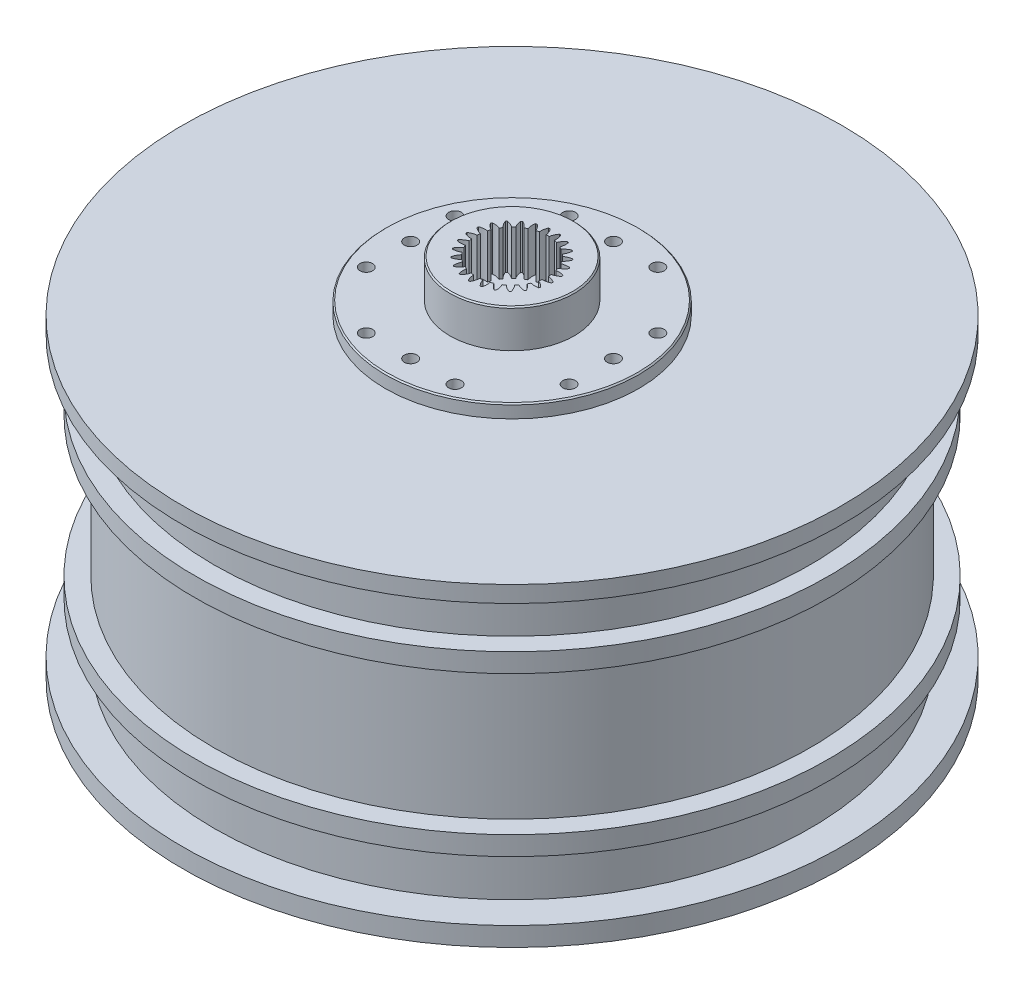
SolidWorks part; units mm, degrees
material "ABS"
ref_plane "正面" through (0, 0, 0) normal (0, 0, 1) x (1, 0, 0)
ref_plane "平面" through (0, 0, 0) normal (0, 1, 0) x (1, 0, 0)
ref_plane "右側面" through (0, 0, 0) normal (1, 0, 0) x (0, 0, -1)
sketch "ｽｹｯﾁ1" plane through (0, 0, 0) normal (0, 1, 0) x (1, 0, 0)
  circle A0 centre (0, 0) radius 10
extrude "ﾎﾞｽ - 押し出し1" add sketch "ｽｹｯﾁ1" along normal blind 2
sketch "ｽｹｯﾁ2" plane through (0, 2, 0) normal (0, 1, 0) x (1, 0, 0)
  circle A0 centre (0, 0) radius 4.9
extrude "ﾎﾞｽ - 押し出し2" add sketch "ｽｹｯﾁ2" along normal blind 3
sketch "ｽｹｯﾁ3" plane through (0, 0, 0) normal (0, -1, 0) x (1, 0, 0)
  line L0 (0, 8) -> (-3.5, 8) construction
  line L1 (0, 0) -> (0, 8) construction
  line L2 (0, 8) -> (3.5, 8) construction
  circle A0 centre (-3.5, 8) radius 0.5
  circle A1 centre (0, 8) radius 0.5
  circle A2 centre (3.5, 8) radius 0.5
  circle A3 centre (8, 0) radius 0.5
  circle A4 centre (8, 3.5) radius 0.5
  circle A5 centre (8, -3.5) radius 0.5
  circle A6 centre (0, -8) radius 0.5
  circle A7 centre (3.5, -8) radius 0.5
  circle A8 centre (-3.5, -8) radius 0.5
  circle A9 centre (-8, 0) radius 0.5
  circle A10 centre (-8, -3.5) radius 0.5
  circle A11 centre (-8, 3.5) radius 0.5
  point P29 (0, 0)
  dimension "D1" = 4
extrude "ｶｯﾄ - 押し出し1" cut sketch "ｽｹｯﾁ3" against normal blind 3
sketch "ｽｹｯﾁ4" plane through (0, 0, 0) normal (0, -1, 0) x (1, 0, 0)
  circle A0 centre (0, 0) radius 4.35
  circle A1 centre (0, 0) radius 2.9
  circle A2 centre (0, 0) radius 1.4
extrude "ｶｯﾄ - 押し出し2" cut sketch "ｽｹｯﾁ4" against normal through all contours A2 region at (0, 0, 0)
extrude "ｶｯﾄ - 押し出し3" cut sketch "ｽｹｯﾁ4<3>" against normal blind 0.45 contours A0 A1 region at (-4.227, 0, 0)
sketch "ｽｹｯﾁ4<3>" plane through (0, 0, 0) normal (0, -1, 0) x (1, 0, 0) same geometry as "ｽｹｯﾁ4"
extrude "ｶｯﾄ - 押し出し4" cut sketch "ｽｹｯﾁ4<4>" against normal blind 0.95 contours A1 A2 region at (-2.818, 0, 0)
sketch "ｽｹｯﾁ4<4>" plane through (0, 0, 0) normal (0, -1, 0) x (1, 0, 0) same geometry as "ｽｹｯﾁ4"
sketch "ｽｹｯﾁ6" plane through (0, 5, 0) normal (0, 1, 0) x (1, 0, 0)
  line L3 (-0.2102, 3.1179) -> (-0.391, 3.0951) construction
  arc A0 (0.1175, 2.809) -> (-0.1175, 2.809) centre (0, 0) ccw
  arc A1 (0.3689, 3.3803) -> (-0.3689, 3.3803) centre (0, 0) ccw
  circle A2 centre (0, 0) radius 3.125 construction
  circle A3 centre (0, 0) radius 2.9365 construction
  arc A4 (-0.1175, 2.809) -> (-0.3689, 3.3803) centre (-1.3511, 2.6072) ccw
  arc A5 (0.3689, 3.3803) -> (0.1175, 2.809) centre (1.3511, 2.6072) ccw
  arc A6 (1.1979, 3.1824) -> (0.8124, 2.6916) centre (1.9571, 2.1893) ccw
  arc A7 (0.8124, 2.6916) -> (0.5847, 2.75) centre (0, 0) ccw
  arc A8 (0.5847, 2.75) -> (0.4834, 3.3659) centre (-0.6603, 2.8613) ccw
  arc A9 (1.1979, 3.1824) -> (0.4834, 3.3659) centre (0, 0) ccw
  arc A10 (1.9517, 2.7845) -> (1.4563, 2.405) centre (2.4401, 1.6338) ccw
  arc A11 (1.4563, 2.405) -> (1.2503, 2.5182) centre (0, 0) ccw
  arc A12 (1.2503, 2.5182) -> (1.3052, 3.1399) centre (0.072, 2.9357) ccw
  arc A13 (1.9517, 2.7845) -> (1.3052, 3.1399) centre (0, 0) ccw
  arc A14 (2.5829, 2.2116) -> (2.0086, 1.9672) centre (2.7697, 0.9757) ccw
  arc A15 (2.0086, 1.9672) -> (1.8372, 2.1282) centre (0, 0) ccw
  arc A16 (1.8372, 2.1282) -> (2.0451, 2.7167) centre (0.7998, 2.8255) ccw
  arc A17 (2.5829, 2.2116) -> (2.0451, 2.7167) centre (0, 0) ccw
  arc A18 (3.0518, 1.4998) -> (2.4347, 1.4059) centre (2.9253, 0.2562) ccw
  arc A19 (2.4347, 1.4059) -> (2.3088, 1.6044) centre (0, 0) ccw
  arc A20 (2.3088, 1.6044) -> (2.6565, 2.1227) centre (1.4774, 2.5378) ccw
  arc A21 (3.0518, 1.4998) -> (2.6565, 2.1227) centre (0, 0) ccw
  arc A22 (3.3289, 0.6938) -> (2.7079, 0.7563) centre (2.8972, -0.4793) ccw
  arc A23 (2.7079, 0.7563) -> (2.6352, 0.9798) centre (0, 0) ccw
  arc A24 (2.6352, 0.9798) -> (3.1009, 1.3954) centre (2.0621, 2.0907) ccw
  arc A25 (3.3289, 0.6938) -> (3.1009, 1.3954) centre (0, 0) ccw
  arc A26 (3.3968, -0.1559) -> (2.8109, 0.0591) centre (2.6869, -1.1848) ccw
  arc A27 (2.8109, 0.0591) -> (2.7961, 0.2937) centre (0, 0) ccw
  arc A28 (2.7961, 0.2937) -> (3.3505, 0.5804) centre (2.5173, 1.5122) ccw
  arc A29 (3.3968, -0.1559) -> (3.3505, 0.5804) centre (0, 0) ccw
  arc A30 (3.2513, -0.9958) -> (2.7373, -0.6418) centre (2.3079, -1.8158) ccw
  arc A31 (2.7373, -0.6418) -> (2.7813, -0.4109) centre (0, 0) ccw
  arc A32 (2.7813, -0.4109) -> (3.3896, -0.2711) centre (2.8142, 0.8387) ccw
  arc A33 (3.2513, -0.9958) -> (3.3896, -0.2711) centre (0, 0) ccw
  arc A34 (2.9016, -1.7731) -> (2.4917, -1.3024) centre (1.7838, -2.3327) ccw
  arc A35 (2.4917, -1.3024) -> (2.5917, -1.0897) centre (0, 0) ccw
  arc A36 (2.5917, -1.0897) -> (3.2157, -1.1055) centre (2.9344, 0.1124) ccw
  arc A37 (2.9016, -1.7731) -> (3.2157, -1.1055) centre (0, 0) ccw
  arc A38 (2.3695, -2.4389) -> (2.0895, -1.8811) centre (1.1477, -2.703) ccw
  arc A39 (2.0895, -1.8811) -> (2.2393, -1.7) centre (0, 0) ccw
  arc A40 (2.2393, -1.7) -> (2.8397, -1.8705) centre (2.8702, -0.6208) ccw
  arc A41 (2.3695, -2.4389) -> (2.8397, -1.8705) centre (0, 0) ccw
  arc A42 (1.6885, -2.9516) -> (1.556, -2.3416) centre (0.4394, -2.9035) ccw
  arc A43 (1.556, -2.3416) -> (1.7462, -2.2035) centre (0, 0) ccw
  arc A44 (1.7462, -2.2035) -> (2.2853, -2.5179) centre (2.6256, -1.3151) ccw
  arc A45 (1.6885, -2.9516) -> (2.2853, -2.5179) centre (0, 0) ccw
  arc A46 (0.9014, -3.2787) -> (0.9248, -2.655) centre (-0.2965, -2.9215) ccw
  arc A47 (0.9248, -2.655) -> (1.1434, -2.5685) centre (0, 0) ccw
  arc A48 (1.1434, -2.5685) -> (1.5874, -3.0072) centre (2.216, -1.9268) ccw
  arc A49 (0.9014, -3.2787) -> (1.5874, -3.0072) centre (0, 0) ccw
  arc A50 (0.0577, -3.3999) -> (0.2355, -2.8016) centre (-1.0137, -2.756) ccw
  arc A51 (0.2355, -2.8016) -> (0.4687, -2.7722) centre (0, 0) ccw
  arc A52 (0.4687, -2.7722) -> (0.7896, -3.3074) centre (1.6673, -2.4173) ccw
  arc A53 (0.0577, -3.3999) -> (0.7896, -3.3074) centre (0, 0) ccw
  arc A54 (-0.7896, -3.3074) -> (-0.4687, -2.7722) centre (-1.6673, -2.4173) ccw
  arc A55 (-0.4687, -2.7722) -> (-0.2355, -2.8016) centre (0, 0) ccw
  arc A56 (-0.2355, -2.8016) -> (-0.0577, -3.3999) centre (1.0137, -2.756) ccw
  arc A57 (-0.7896, -3.3074) -> (-0.0577, -3.3999) centre (0, 0) ccw
  arc A58 (-1.5874, -3.0072) -> (-1.1434, -2.5685) centre (-2.216, -1.9268) ccw
  arc A59 (-1.1434, -2.5685) -> (-0.9248, -2.655) centre (0, 0) ccw
  arc A60 (-0.9248, -2.655) -> (-0.9014, -3.2787) centre (0.2965, -2.9215) ccw
  arc A61 (-1.5874, -3.0072) -> (-0.9014, -3.2787) centre (0, 0) ccw
  arc A62 (-2.2853, -2.5179) -> (-1.7462, -2.2035) centre (-2.6256, -1.3151) ccw
  arc A63 (-1.7462, -2.2035) -> (-1.556, -2.3416) centre (0, 0) ccw
  arc A64 (-1.556, -2.3416) -> (-1.6885, -2.9516) centre (-0.4394, -2.9035) ccw
  arc A65 (-2.2853, -2.5179) -> (-1.6885, -2.9516) centre (0, 0) ccw
  arc A66 (-2.8397, -1.8705) -> (-2.2393, -1.7) centre (-2.8702, -0.6208) ccw
  arc A67 (-2.2393, -1.7) -> (-2.0895, -1.8811) centre (0, 0) ccw
  arc A68 (-2.0895, -1.8811) -> (-2.3695, -2.4389) centre (-1.1477, -2.703) ccw
  arc A69 (-2.8397, -1.8705) -> (-2.3695, -2.4389) centre (0, 0) ccw
  arc A70 (-3.2157, -1.1055) -> (-2.5917, -1.0897) centre (-2.9344, 0.1124) ccw
  arc A71 (-2.5917, -1.0897) -> (-2.4917, -1.3024) centre (0, 0) ccw
  arc A72 (-2.4917, -1.3024) -> (-2.9016, -1.7731) centre (-1.7838, -2.3327) ccw
  arc A73 (-3.2157, -1.1055) -> (-2.9016, -1.7731) centre (0, 0) ccw
  arc A74 (-3.3896, -0.2711) -> (-2.7813, -0.4109) centre (-2.8142, 0.8387) ccw
  arc A75 (-2.7813, -0.4109) -> (-2.7373, -0.6418) centre (0, 0) ccw
  arc A76 (-2.7373, -0.6418) -> (-3.2513, -0.9958) centre (-2.3079, -1.8158) ccw
  arc A77 (-3.3896, -0.2711) -> (-3.2513, -0.9958) centre (0, 0) ccw
  arc A78 (-3.3505, 0.5804) -> (-2.7961, 0.2937) centre (-2.5173, 1.5122) ccw
  arc A79 (-2.7961, 0.2937) -> (-2.8109, 0.0591) centre (0, 0) ccw
  arc A80 (-2.8109, 0.0591) -> (-3.3968, -0.1559) centre (-2.6869, -1.1848) ccw
  arc A81 (-3.3505, 0.5804) -> (-3.3968, -0.1559) centre (0, 0) ccw
  arc A82 (-3.1009, 1.3954) -> (-2.6352, 0.9798) centre (-2.0621, 2.0907) ccw
  arc A83 (-2.6352, 0.9798) -> (-2.7079, 0.7563) centre (0, 0) ccw
  arc A84 (-2.7079, 0.7563) -> (-3.3289, 0.6938) centre (-2.8972, -0.4793) ccw
  arc A85 (-3.1009, 1.3954) -> (-3.3289, 0.6938) centre (0, 0) ccw
  arc A86 (-2.6565, 2.1227) -> (-2.3088, 1.6044) centre (-1.4774, 2.5378) ccw
  arc A87 (-2.3088, 1.6044) -> (-2.4347, 1.4059) centre (0, 0) ccw
  arc A88 (-2.4347, 1.4059) -> (-3.0518, 1.4998) centre (-2.9253, 0.2562) ccw
  arc A89 (-2.6565, 2.1227) -> (-3.0518, 1.4998) centre (0, 0) ccw
  arc A90 (-2.0451, 2.7167) -> (-1.8372, 2.1282) centre (-0.7998, 2.8255) ccw
  arc A91 (-1.8372, 2.1282) -> (-2.0086, 1.9672) centre (0, 0) ccw
  arc A92 (-2.0086, 1.9672) -> (-2.5829, 2.2116) centre (-2.7697, 0.9757) ccw
  arc A93 (-2.0451, 2.7167) -> (-2.5829, 2.2116) centre (0, 0) ccw
  arc A94 (-1.3052, 3.1399) -> (-1.2503, 2.5182) centre (-0.072, 2.9357) ccw
  arc A95 (-1.2503, 2.5182) -> (-1.4563, 2.405) centre (0, 0) ccw
  arc A96 (-1.4563, 2.405) -> (-1.9517, 2.7845) centre (-2.4401, 1.6338) ccw
  arc A97 (-1.3052, 3.1399) -> (-1.9517, 2.7845) centre (0, 0) ccw
  arc A98 (-0.4834, 3.3659) -> (-0.5847, 2.75) centre (0.6603, 2.8613) ccw
  arc A99 (-0.5847, 2.75) -> (-0.8124, 2.6916) centre (0, 0) ccw
  arc A100 (-0.8124, 2.6916) -> (-1.1979, 3.1824) centre (-1.9571, 2.1893) ccw
  arc A101 (-0.4834, 3.3659) -> (-1.1979, 3.1824) centre (0, 0) ccw
  circle A102 centre (0, 0) radius 2.8115
  circle A103 centre (0, 0) radius 3.4004
  point P158 (0, 0)
  dimension "D1" = 25
extrude "ｶｯﾄ - 押し出し5" cut sketch "ｽｹｯﾁ6" against normal blind 3.5 contours A51 A102 A47 A43 A39 A35 A31 A27 A23 A19 A15 A11 A7 A0 A99 A95 A91 A87 A83 A79 A75 A71 A67 A63 A59 A55 | A80 A103 A74 A102 | A84 A103 A78 A102 | A88 A103 A82 A102 | A92 A103 A86 A102 | A96 A103 A90 A102 | A100 A103 A94 A102 | A4 A103 A98 A102 | A8 A103 A5 A102 | A12 A103 A6 A102 | A16 A103 A10 A102 | A20 A103 A14 A102 | A24 A103 A18 A102 | A28 A103 A22 A102 | A32 A103 A26 A102 | A36 A103 A30 A102 | A40 A103 A34 A102 | A44 A103 A38 A102 | A48 A103 A42 A102 | A52 A103 A46 A102 | A56 A103 A50 A102 | A60 A103 A54 A102 | A64 A103 A58 A102 | A68 A103 A62 A102 | A72 A103 A66 A102 | A76 A103 A70 A102 region at (0, 5, 0) region at (0.3828, 5, -3.0303) region at (-0.3828, 5, -3.0303) region at (1.1244, 5, -2.8399) region at (-1.1244, 5, -2.8399) region at (1.7953, 5, -2.471) region at (-1.7953, 5, -2.471) region at (2.3534, 5, -1.9469) region at (-2.3534, 5, -1.9469) region at (2.7637, 5, -1.3005) region at (-2.7637, 5, -1.3005) region at (3.0003, 5, -0.5723) region at (-3.0003, 5, -0.5723) region at (3.0483, 5, 0.1918) region at (-3.0483, 5, 0.1918) region at (-2.9049, 5, 0.9439) region at (2.9049, 5, 0.9439) region at (-2.5789, 5, 1.6366) region at (2.5789, 5, 1.6366) region at (-2.0909, 5, 2.2265) region at (2.0909, 5, 2.2265) region at (-1.4715, 5, 2.6766) region at (1.4715, 5, 2.6766) region at (-0.7596, 5, 2.9584) region at (0.7596, 5, 2.9584) region at (0, 5, 3.0544)
chamfer "面取り1" distance 0.1 angle 45 3 edges at (0, 0, 10) (0, 2, 10) (0, 5, 4.9)
sketch "ｽｹｯﾁ11" plane through (0, 0, 0) normal (0, 0, 1) x (1, 0, 0)
  line L0 (18.5, -23.85) -> (23.5, -23.85)
  line L1 (2.9, 0.95) -> (23.5, 0.95)
  line L4 (23.5, -0.35) -> (23.5, -4.35)
  line L8 (2.9, 0.95) -> (2.9, -4.05)
  line L9 (23.5, -18.35) -> (23.5, -22.35)
  line L10 (2.9, 0.95) -> (26, 0.95)
  line L11 (2.9, 0.95) -> (2.9, -0.35)
  line L12 (23.5, -0.35) -> (26, -0.35)
  line L13 (26, 0.95) -> (26, -0.35)
  line L14 (23.5, -4.35) -> (25, -4.35)
  line L16 (23.5, -5.85) -> (25, -5.85)
  line L17 (25, -4.35) -> (25, -5.85)
  line L18 (23.5, -16.85) -> (25, -16.85)
  line L21 (25, -16.85) -> (25, -18.35)
  line L22 (18.5, -23.85) -> (26, -23.85)
  line L24 (23.5, -22.35) -> (26, -22.35)
  line L25 (26, -23.85) -> (26, -22.35)
  line L28 (2.9, -4.05) -> (18.5, -4.05)
  line L29 (18.5, -23.85) -> (18.5, -4.05)
  line L30 (23.5, -18.35) -> (25, -18.35)
  line L31 (23.5, -5.85) -> (23.5, -16.85)
  line L32 (23.5, -23.85) -> (26, -23.85)
  dimension "D2" = 24.8
  dimension "D4" = 1.3
  dimension "D5" = 23.1
  dimension "D6" = 1.5
  dimension "D7" = 4
  dimension "D8" = 22.1
  dimension "D9" = 1.5
  dimension "D10" = 11
  dimension "D11" = 22.1
  dimension "D12" = 23.1
  dimension "D14" = 5
  dimension "D15" = 5
sketch "ｽｹｯﾁ13" plane through (0, 0, 0) normal (0, 0, 1) x (1, 0, 0)
  line L0 (0, 0) -> (0, 6.7532)
revolve "回転1" add sketch "ｽｹｯﾁ11" angle 360 about L0 region at (18.8389, -13.95, 0)
sketch "ｽｹｯﾁ14" plane through (0, 0, 0) normal (0, 0, 1) x (1, 0, 0)
  line L0 (-20.0887, -3.1222) -> (-20.0887, -16.8787)
  line L1 (-20.0887, -16.8787) -> (-10.3358, -3.1222)
  line L2 (-10.3358, -3.1222) -> (-20.0887, -3.1222)
extrude "ﾎﾞｽ - 押し出し4" add sketch "ｽｹｯﾁ14" along normal blind 2 and the other way blind 2
pattern_circular "円形ﾊﾟﾀｰﾝ1" count 5 every 72 about axis through (0, 0, 0) along (0, 1, 0) of "ﾎﾞｽ - 押し出し4"
